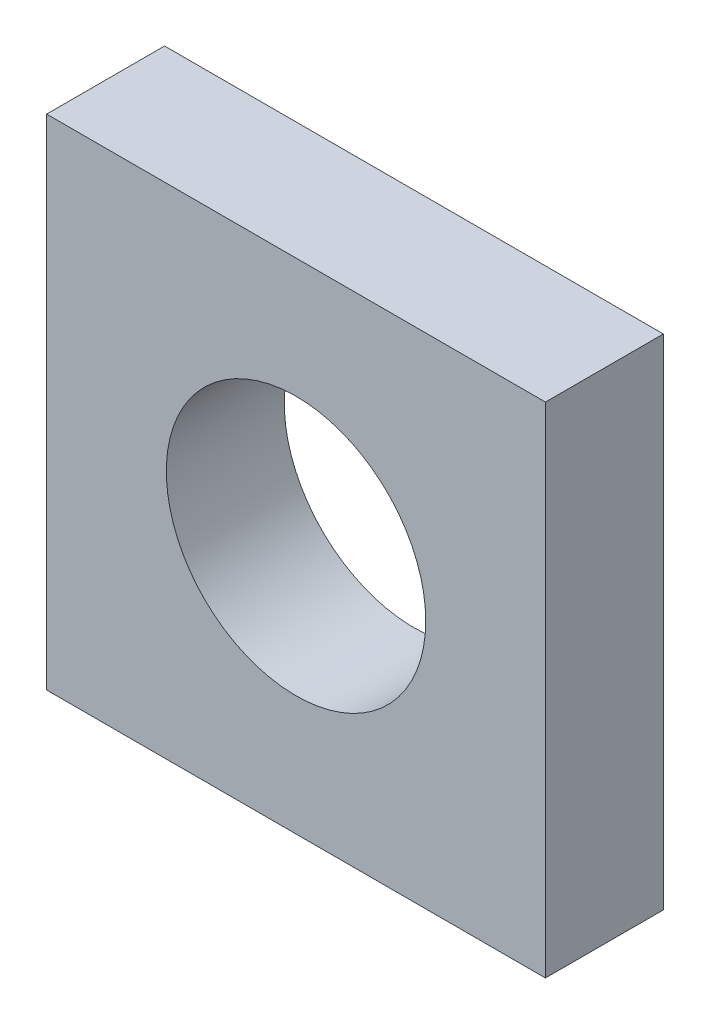
SolidWorks part; units mm, degrees
ref_plane "Front Plane" through (0, 0, 0) normal (0, 0, 1) x (1, 0, 0)
ref_plane "Top Plane" through (0, 0, 0) normal (0, 1, 0) x (1, 0, 0)
ref_plane "Right Plane" through (0, 0, 0) normal (1, 0, 0) x (0, 0, -1)
sketch "Sketch1" plane through (0, 0, 0) normal (0, 0, 1) x (1, 0, 0)
  line L1 (-21.15, -21.15) -> (21.15, -21.15)
  line L2 (-21.15, -21.15) -> (-21.15, 21.15)
  line L3 (-21.15, 21.15) -> (21.15, 21.15)
  line L4 (21.15, -21.15) -> (21.15, 21.15)
  line L5 (-21.15, -21.15) -> (21.15, 21.15) construction
  line L6 (-21.15, 21.15) -> (21.15, -21.15) construction
  circle A0 centre (0, 0) radius 11
  point P0 (0, 0)
  dimension "D3" = 22
  dimension "D1" = 21.15
extrude "Boss-Extrude1" add sketch "Sketch1" along normal blind 10
